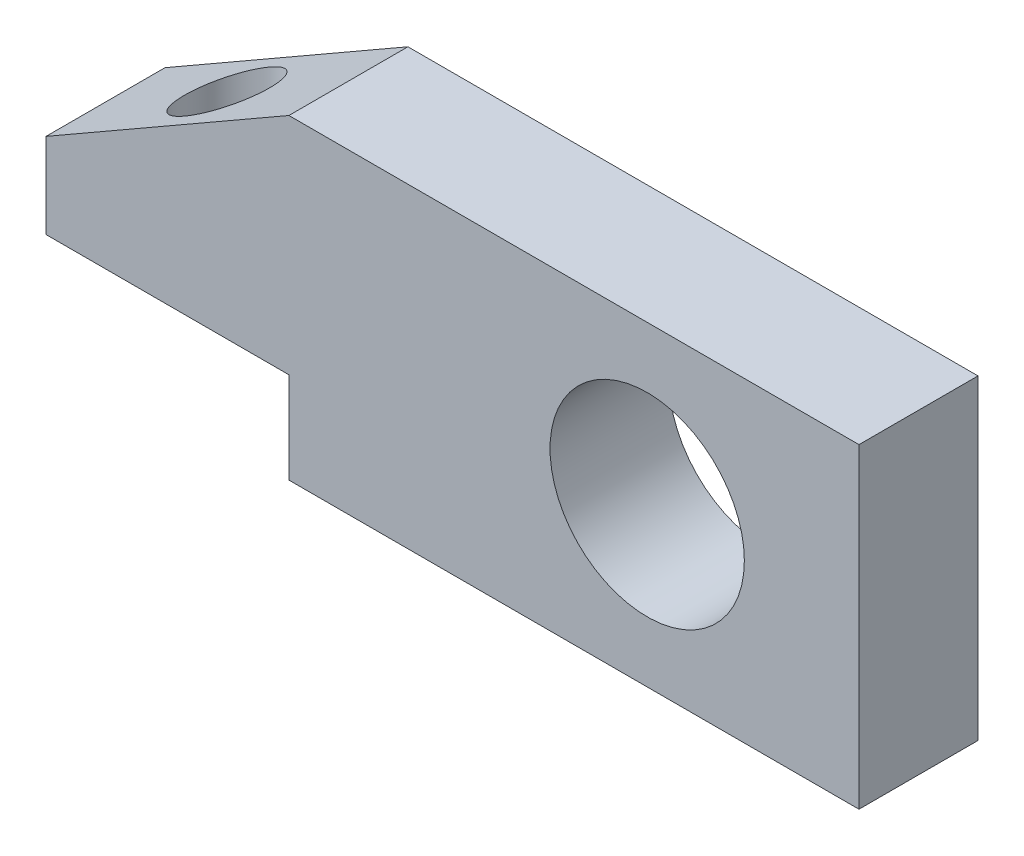
SolidWorks part; units mm, degrees
material "ABS"
ref_plane "Front Plane" through (0, 0, 0) normal (0, 0, 1) x (1, 0, 0)
ref_plane "Top Plane" through (0, 0, 0) normal (0, 1, 0) x (1, 0, 0)
ref_plane "Right Plane" through (0, 0, 0) normal (1, 0, 0) x (0, 0, -1)
sketch "Sketch1" plane through (0, 0, 0) normal (0, 0, 1) x (1, 0, 0)
  line L0 (-24, 15) -> (0, 15)
  line L1 (0, 15) -> (0, 0)
  line L2 (0, 0) -> (93, 0)
  line L3 (93, 0) -> (93, 102.7)
  line L4 (93, 102.7) -> (0, 102.7)
  line L5 (0, 102.7) -> (0, 30)
  line L6 (0, 30) -> (-24, 30)
  line L7 (-24, 30) -> (-24, 15)
  circle A0 centre (15, 10.5) radius 8
  circle A1 centre (70, 72) radius 11
  circle A2 centre (15, 10.5) radius 11
  dimension "D1" = 15
  dimension "D10" = 16
  dimension "D11" = 22
  dimension "D12" = 22
  dimension "D2" = 24
  dimension "D3" = 72.7
  dimension "D4" = 15
  dimension "D5" = 15
  dimension "D6" = 10.5
  dimension "D7" = 82.5061
  dimension "D8" = 72
  dimension "D9" = 93
extrude "Boss-Extrude1" add sketch "Sketch1" along normal blind 4.8 contours A2 L2 L3 L4 L5 L6 L7 L0 L1 A1 | L2 A2 A0 region at (44.5238, 51.0418, 0) region at (8.6656, 19.1141, 0)
sketch "Sketch2" plane through (0, 0, 4.8) normal (0, 0, 1) x (1, 0, 0)
  line L0 (93, 0) -> (93, 102.7) construction
  line L1 (48.1786, 92.7632) -> (93, 92.7632)
  line L2 (48.1786, 92.7632) -> (48.1786, 52.666)
  line L3 (48.1786, 52.666) -> (93, 52.666)
  line L4 (93, 92.7632) -> (93, 52.666)
  line L5 (48.1786, 92.7632) -> (93, 52.666) construction
  line L6 (48.1786, 52.666) -> (93, 92.7632) construction
  circle A0 centre (70, 72) radius 11
  circle A1 centre (70, 72) radius 4.15
  point P8 (70.5893, 72.7146)
  line M4 (93, 0) -> (93, 102.7)
  circle M10 centre (70, 72) radius 11
  dimension "D1" = 22
  dimension "D2" = 8.3
extrude "Boss-Extrude2" add sketch "Sketch2" along normal blind 8.2 contours L2 L3 L1 M4 M10 region at (70.5893, 92.1618, 4.8)
sketch "Sketch3" plane through (0, 0, 4.8) normal (0, 0, 1) x (1, 0, 0)
  line L1 (-24, 15) -> (0, 15)
  line L2 (-24, 15) -> (-24, 30)
  line L3 (-24, 30) -> (0, 30)
  line L4 (0, 15) -> (0, 30)
  line L5 (-24, 15) -> (0, 30) construction
  line L6 (-24, 30) -> (0, 15) construction
  line L7 (0, 0) -> (93, 0)
  line L8 (0, 0) -> (0, 52.666)
  line L9 (0, 52.666) -> (93, 52.666)
  line L10 (93, 0) -> (93, 52.666)
  circle A0 centre (15, 10.5) radius 8
  point P4 (-12, 22.5)
  point P11 (46.5, 26.333)
  circle M1 centre (15, 10.5) radius 8
  line M6 (0, 102.7) -> (0, 30)
  line M7 (0, 30) -> (-24, 30)
  line M8 (-24, 30) -> (-24, 15)
  line M9 (-24, 15) -> (0, 15)
  line M10 (0, 15) -> (0, 0)
  line M11 (0, 0) -> (93, 0)
  line M12 (93, 0) -> (93, 52.666)
  line M13 (93, 52.666) -> (48.1786, 52.666)
  dimension "D1" = 93
extrude "Boss-Extrude3" add sketch "Sketch3" along normal blind 5 contours L4 M9 M7 M8 | L9 L4 M6 M10 M11 M12 M13 M1 region at (-12, 22.5, 4.8) region at (47.8484, 27.0108, 4.8)
sketch "Sketch4" plane through (0, 83.2317, 0) normal (0, -1, 0) x (1, 0, 0)
  line L0 (0, 9.8) -> (0, 4.8) construction
  line L1 (0, 4.8) -> (48.1786, 4.8)
  line L2 (0, 4.8) -> (0, 45.3)
  line L3 (0, 45.3) -> (48.1786, 45.3)
  line L4 (48.1786, 4.8) -> (48.1786, 45.3)
  line L5 (0, 4.8) -> (48.1786, 45.3) construction
  line L6 (0, 45.3) -> (48.1786, 4.8) construction
  line L7 (0, 4.8) -> (48.1786, 4.8) construction
  line L8 (48.1786, 13) -> (48.1786, 9.8) construction
  line L9 (0, 0) -> (93, 0) construction
  line L10 (0, 45.3) -> (-5, 45.3)
  line L11 (0, 45.3) -> (0, 0)
  line L12 (0, 0) -> (-5, 0)
  line L13 (-5, 45.3) -> (-5, 0)
  line L14 (0, 45.3) -> (-5, 0) construction
  line L15 (0, 0) -> (-5, 45.3) construction
  circle A0 centre (13.9465, 30.3) radius 6.35
  circle A1 centre (13.9465, 23.3) radius 18.5
  circle A3 centre (29.4465, 23.3) radius 2
  circle A4 centre (21.6965, 9.8766) radius 2
  circle A5 centre (6.1965, 9.8766) radius 2
  point P10 (24.0893, 25.05)
  point P30 (-2.5, 22.65)
  arc M5 (5.039, 30.9329) -> (22.854, 30.9329) centre (13.9465, 30.3) ccw
  arc M7 (23.1854, 31.0672) -> (4.7077, 31.0672) centre (13.9465, 23.3) cw
  circle M9 centre (21.6965, 9.8766) radius 1.6
  circle M10 centre (6.1965, 9.8766) radius 1.6
  circle M11 centre (-1.5535, 23.3) radius 1.6
  circle M12 centre (6.1965, 36.7234) radius 1.6
  circle M13 centre (21.6965, 36.7234) radius 1.6
  circle M15 centre (27.3699, 31.05) radius 2.1
  circle M16 centre (0.5231, 31.05) radius 2.1
  circle M17 centre (13.9465, 7.8) radius 2.1
  circle M19 centre (13.9465, 23.3) radius 18.5
  dimension "D1" = 12.7
  dimension "D2" = 15
  dimension "D3" = 4
  dimension "D4" = 4
  dimension "D5" = 4
  dimension "D6" = 5
  dimension "D7" = 0
extrude "Boss-Extrude4" add sketch "Sketch4" along normal blind 5 contours L1 L4 L3 M19 | A0 L3 L2 A5 A4 A3 M12 M19 M16 M11 M13 M17 M15 M5 M7 | M5 M7 | M17 | A4 M9 | M9 | M10 | A5 M10 | M15 | L2 M16 | L2 L1 M19 region at (3.3557, 83.2317, 6.6306) region at (34.3643, 83.2317, 27.4815) region at (15.1399, 83.2317, 22.3686) region at (1.1393, 83.2317, 31.05) region at (19.7531, 83.2317, 9.8766) region at (4.2531, 83.2317, 9.8766) region at (21.6965, 83.2317, 9.8766) region at (6.1965, 83.2317, 9.8766) region at (27.3699, 83.2317, 31.05) region at (13.9465, 83.2317, 7.8)
sketch "Sketch5" plane through (48.1786, 0, 0) normal (1, 0, 0) x (0, 0, -1)
  line L0 (-45.3, 83.2317) -> (-13, 92.7632)
  line L1 (-13, 92.7632) -> (-4.8, 92.7632)
  line L2 (-4.8, 92.7632) -> (-4.8, 78.2317)
  line L3 (-4.8, 78.2317) -> (-45.3, 78.2317)
  line L4 (-45.3, 78.2317) -> (-45.3, 83.2317)
extrude "Boss-Extrude5" add sketch "Sketch5" against normal blind 5
sketch "Sketch6" plane through (0, 0, 4.8) normal (0, 0, 1) x (1, 0, 0)
  line L0 (0, 78.2317) -> (0, 52.666) construction
  line L1 (0, 78.2317) -> (48.1786, 78.2317)
  line L2 (0, 78.2317) -> (0, 52.666)
  line L3 (0, 52.666) -> (48.1786, 52.666)
  line L4 (48.1786, 78.2317) -> (48.1786, 52.666)
  line L5 (0, 78.2317) -> (48.1786, 52.666) construction
  line L6 (0, 52.666) -> (48.1786, 78.2317) construction
  line L7 (0, 78.2317) -> (48.1786, 78.2317) construction
  point P4 (24.0893, 65.4489)
extrude "Boss-Extrude6" add sketch "Sketch6" along normal up to surface (5 mm away) up to face at (20.6865, 27.5553, 9.8)
ref_plane "Plane1" through (3.9877, 7.5909, 34.4544) normal (0.9262, 0.2454, -0.2862) x (0.0581, -0.8429, -0.5349)
sketch "Sketch8" plane through (0, 30, 0) normal (0, 1, 0) x (1, 0, 0)
  line L0 (0, 0) -> (-24, -9.8)
  line L1 (-24, -9.8) -> (-24, 0)
  line L2 (-24, 0) -> (0, -9.8)
  circle A0 centre (-12, -4.9) radius 2
  dimension "D1" = 4
extrude "Cut-Extrude1" cut sketch "Sketch8" against normal through all contours A0
sketch "Sketch9" plane through (0, 0, 0) normal (0, 0, -1) x (-1, 0, 0)
  line L1 (0, 30) -> (-93, 30)
  line L2 (0, 30) -> (0, 102.7)
  line L3 (0, 102.7) -> (-93, 102.7)
  line L4 (-93, 30) -> (-93, 102.7)
extrude "Cut-Extrude2" cut sketch "Sketch9" against normal blind 100
sketch "Sketch10" plane through (0, 0, 9.8) normal (0, 0, 1) x (1, 0, 0)
  line L0 (93, 30) -> (-24, 30) construction
  line L1 (93, 0) -> (26.438, 0)
  line L2 (93, 0) -> (93, 30)
  line L3 (93, 30) -> (26.438, 30)
  line L4 (26.438, 0) -> (26.438, 30)
extrude "Cut-Extrude3" cut sketch "Sketch10" against normal blind 100
sketch "Sketch11" plane through (0, 0, 0) normal (0, 0, -1) x (-1, 0, 0)
  line L0 (24, 30) -> (24, 15) construction
  line L1 (0, 15) -> (24, 15)
  line L2 (0, 15) -> (0, 30)
  line L3 (0, 30) -> (24, 30)
  line L4 (24, 15) -> (24, 30)
  line L5 (-26.438, 30) -> (24, 30) construction
extrude "Boss-Extrude7" add sketch "Sketch11" along normal blind 12
sketch "Sketch13" plane through (-24, 0, 0) normal (-1, 0, 0) x (0, 0, 1)
  line L0 (9.8, 30) -> (9.8, 15) construction
  line L1 (-12, 30) -> (9.8, 30)
  line L2 (-12, 30) -> (-12, 25)
  line L3 (-12, 25) -> (9.8, 25)
  line L4 (9.8, 30) -> (9.8, 25)
  dimension "D1" = 5
extrude "Cut-Extrude4" cut sketch "Sketch13" against normal blind 200
sketch "Sketch15" plane through (0, 25, 0) normal (0, 1, 0) x (1, 0, 0)
  circle A0 centre (-12, 5.1) radius 2
  circle A1 centre (-12, -4.9) radius 2 construction
  dimension "D1" = 4
  dimension "D2" = 10
  dimension "D3" = 0
extrude "Cut-Extrude5" cut sketch "Sketch15" against normal blind 200
sketch "Sketch16" plane through (0, 25, 0) normal (0, 1, 0) x (1, 0, 0)
  line L1 (0, 0) -> (-24, 0)
  line L2 (0, 0) -> (0, 12)
  line L3 (0, 12) -> (-24, 12)
  line L4 (-24, 0) -> (-24, 12)
extrude "Cut-Extrude6" cut sketch "Sketch16" against normal blind 10
sketch "Sketch17" plane through (0, 0, 0) normal (0, 0, -1) x (-1, 0, 0)
  line L0 (24, 15) -> (24, 25) construction
  line L1 (0, 15) -> (24, 15)
  line L2 (0, 15) -> (0, 19.51)
  line L3 (0, 19.51) -> (24, 19.51)
  line L4 (24, 15) -> (24, 19.51)
  line L5 (0, 15) -> (24, 19.51) construction
  line L6 (0, 19.51) -> (24, 15) construction
  point P4 (12, 17.255)
extrude "Cut-Extrude7" cut sketch "Sketch17" against normal through all
sketch "Sketch18" plane through (0, 25, 0) normal (0, 1, 0) x (1, 0, 0)
  line L1 (26.438, 0) -> (-0.002, 0)
  line L2 (26.438, 0) -> (26.438, -9.8)
  line L3 (26.438, -9.8) -> (-0.002, -9.8)
  line L4 (-0.002, 0) -> (-0.002, -9.8)
  dimension "D1" = 26.44
extrude "Boss-Extrude8" add sketch "Sketch18" along normal blind 14.5
sketch "Sketch19" plane through (0, 0, 0) normal (-1, 0, 0) x (0, 0, 1)
  line L0 (0, 19.51) -> (0, 0) construction
  line L1 (0, 5.01) -> (9.8, 5.01)
  line L2 (0, 5.01) -> (0, 12.01)
  line L3 (0, 12.01) -> (9.8, 12.01)
  line L4 (9.8, 5.01) -> (9.8, 12.01)
  line L5 (9.8, 19.51) -> (9.8, 0) construction
  line L8 (9.8, 19.51) -> (0, 19.51) construction
  dimension "D1" = 14.5
  dimension "D2" = 7
extrude "Boss-Extrude9" add sketch "Sketch19" along normal blind 34.5
sketch "Sketch20" plane through (0, 5.01, 0) normal (0, -1, 0) x (1, 0, 0)
  line L0 (-34.5, 9.8) -> (0, 9.8) construction
  line L1 (-34.5, 0) -> (-34.5, 9.8) construction
  circle A1 centre (-24.5, 4.9) radius 2
  dimension "D1" = 4
  dimension "D2" = 4.9
  dimension "D3" = 10
extrude "Cut-Extrude8" cut sketch "Sketch20" against normal blind 20
sketch "Sketch21" plane through (0, 0, 0) normal (0, 0, -1) x (-1, 0, 0)
  line L1 (24, 25) -> (0, 25)
  line L2 (24, 25) -> (24, 19.51)
  line L3 (24, 19.51) -> (0, 19.51)
  line L4 (0, 25) -> (0, 19.51)
extrude "Cut-Extrude9" cut sketch "Sketch21" against normal blind 20
sketch "Sketch22" plane through (0, 0, 0) normal (0, 0, -1) x (-1, 0, 0)
  line L0 (-26.438, 39.5) -> (-26.438, 0) construction
  line L1 (0.002, 39.5) -> (-26.438, 39.5)
  line L2 (0.002, 39.5) -> (0.002, 23.5)
  line L3 (0.002, 23.5) -> (-26.438, 23.5)
  line L4 (-26.438, 39.5) -> (-26.438, 23.5)
  circle A0 centre (-15, 10.5) radius 8 construction
  dimension "D1" = 13
extrude "Cut-Extrude10" cut sketch "Sketch22" against normal blind 20
sketch "Sketch23" plane through (0, 0, 0) normal (0, -1, 0) x (1, 0, 0)
  line L1 (0, 0) -> (26.438, 0)
  line L2 (0, 0) -> (0, 9.8)
  line L3 (0, 9.8) -> (26.438, 9.8)
  line L4 (26.438, 0) -> (26.438, 9.8)
extrude "Boss-Extrude10" add sketch "Sketch23" along normal blind 2.5
sketch "Sketch24" plane through (0, 0, 0) normal (-1, 0, 0) x (0, 0, 1)
  line L1 (0, -2.5) -> (9.8, -2.5)
  line L2 (0, -2.5) -> (0, 23.5)
  line L3 (0, 23.5) -> (9.8, 23.5)
  line L4 (9.8, -2.5) -> (9.8, 23.5)
extrude "Boss-Extrude11" add sketch "Sketch24" along normal blind 14.5
sketch "Sketch25" plane through (0, 0, 0) normal (0, 0, -1) x (-1, 0, 0)
  line L0 (14.5, 12.01) -> (14.5, 23.5)
  line L2 (14.5, 23.5) -> (14.5, 12.01) construction
  line L3 (14.5, 23.5) -> (34.5, 12.01)
  line L4 (34.5, 12.01) -> (14.5, 12.01)
extrude "Boss-Extrude12" add sketch "Sketch25" against normal up to vertex (9.8 mm away) up to point (-34.5, 12.01, 9.8)
sketch "Sketch26" plane through (0, 12.01, 0) normal (0, -1, 0) x (1, 0, 0)
  circle A0 centre (-24.5, 4.9) radius 3.5
  dimension "D1" = 7
extrude "Cut-Extrude11" cut sketch "Sketch26" against normal blind 14.5
sketch "Sketch28" plane through (26.438, 0, 0) normal (1, 0, 0) x (0, 0, -1)
  line L1 (0, -2.5) -> (-9.8, -2.5)
  line L2 (0, -2.5) -> (0, 23.5)
  line L3 (0, 23.5) -> (-9.8, 23.5)
  line L4 (-9.8, -2.5) -> (-9.8, 23.5)
extrude "Boss-Extrude13" add sketch "Sketch28" along normal blind 6
